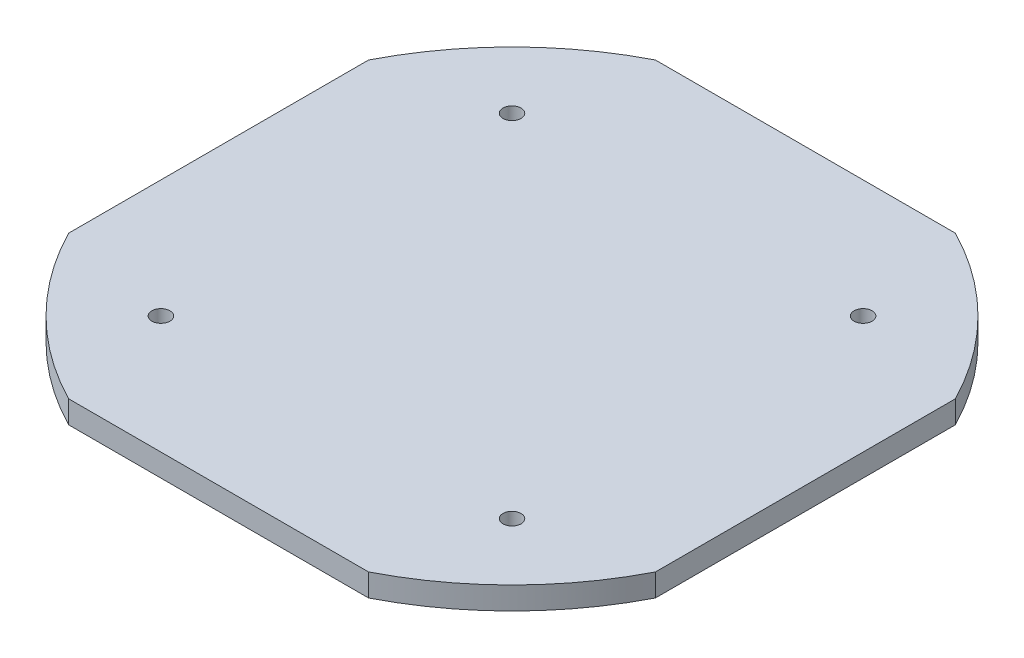
SolidWorks part; units mm, degrees
ref_plane "Front Plane" through (0, 0, 0) normal (0, 0, 1) x (1, 0, 0)
ref_plane "Top Plane" through (0, 0, 0) normal (0, 1, 0) x (1, 0, 0)
ref_plane "Right Plane" through (0, 0, 0) normal (1, 0, 0) x (0, 0, -1)
sketch "Sketch1" plane through (0, 0, 0) normal (0, 1, 0) x (1, 0, 0)
  line L0 (65, 33.2265) -> (65, -33.2265)
  line L1 (65, 33.2265) -> (0, 0) construction
  line L2 (0, 0) -> (65, -33.2265) construction
  line L3 (33.2265, -65) -> (0, 0) construction
  line L4 (0, 0) -> (-33.2265, -65) construction
  line L5 (33.2265, -65) -> (-33.2265, -65)
  line L6 (-65, -33.2265) -> (0, 0) construction
  line L7 (0, 0) -> (-65, 33.2265) construction
  line L8 (-65, -33.2265) -> (-65, 33.2265)
  line L9 (-33.2265, 65) -> (0, 0) construction
  line L10 (0, 0) -> (33.2265, 65) construction
  line L11 (-33.2265, 65) -> (33.2265, 65)
  arc A0 (-65, -33.2265) -> (-33.2265, -65) centre (0, 0) ccw
  arc A1 (-65, 33.2265) -> (-65, -33.2265) centre (0, 0) ccw construction
  arc A2 (33.2265, 65) -> (-33.2265, 65) centre (0, 0) ccw construction
  arc A3 (-33.2265, 65) -> (-65, 33.2265) centre (0, 0) ccw
  arc A4 (65, -33.2265) -> (65, 33.2265) centre (0, 0) ccw construction
  arc A5 (65, 33.2265) -> (33.2265, 65) centre (0, 0) ccw
  arc A6 (-33.2265, -65) -> (33.2265, -65) centre (0, 0) ccw construction
  arc A7 (33.2265, -65) -> (65, -33.2265) centre (0, 0) ccw
  point P14 (0, 0)
  dimension "D1" = 146
  dimension "D2" = 65
  dimension "D3" = 4
extrude "Boss-Extrude1" add sketch "Sketch1" along normal blind 5
sketch "Sketch2" plane through (0, 5, 0) normal (0, 1, 0) x (1, 0, 0)
  point P0 (37.7109, 0)
  point P2 (0, 39.9735)
  point P4 (-38.2765, 0)
  point P6 (0, -34.694)
sketch "Sketch5" plane through (0, 5, 0) normal (0, 1, 0) x (1, 0, 0)
  line L0 (38.8909, 38.8909) -> (0, 0) construction
  line L1 (0, 0) -> (-38.8909, -38.8909) construction
  line L3 (-38.8909, 38.8909) -> (0, 0) construction
  line L4 (0, 0) -> (38.8909, -38.8909) construction
  line L5 (0, 0) -> (0, 65) construction
  line L6 (33.2265, 65) -> (-33.2265, 65) construction
  point P0 (38.8909, 38.8909)
  point P3 (38.8909, -38.8909)
  point P5 (-38.8909, -38.8909)
  point P7 (-38.8909, 38.8909)
  dimension "D1" = 45
  dimension "D2" = 55
hole_wizard "Ø4.0mm Dowel Hole2" positions "Sketch5" profile "Sketch6" hole size "Ø4.0" standard "ISO" end condition through all
sketch "Sketch6" plane through (38.8909, 5, -38.8909) normal (1, 0, 0) x (0, 0, 1)
  line L0 (0, 0) -> (0, 5)
  line L1 (0, 5) -> (2, 5)
  line L2 (2, 5) -> (2, 0)
  line L5 (2, 0) -> (0, 0)
  line L11 (0, -6.35) -> (0, 107.95) construction
  dimension "Thru Hole Dia." = 4
  dimension "Thru Hole Depth" = 5
sketch "Sketch7" plane through (0, 0, 0) normal (0, -1, 0) x (1, 0, 0)
  line L0 (38.85, -20.1) -> (-38.85, -20.1) construction
  line L1 (-38.85, 20.1) -> (38.85, 20.1) construction
  circle A0 centre (27.8, -9.75) radius 1.7 construction
  circle A1 centre (27.8, 9.75) radius 1.7 construction
  circle A2 centre (-27.8, 9.75) radius 1.7 construction
  circle A3 centre (-27.8, -9.75) radius 1.7 construction
  point P12 (0, 0)
  point P13 (0, 0)
sketch "Sketch8" plane through (0, 5, 0) normal (0, 1, 0) x (1, 0, 0)
  circle A0 centre (0, 0) radius 10 construction
  dimension "D1" = 20
